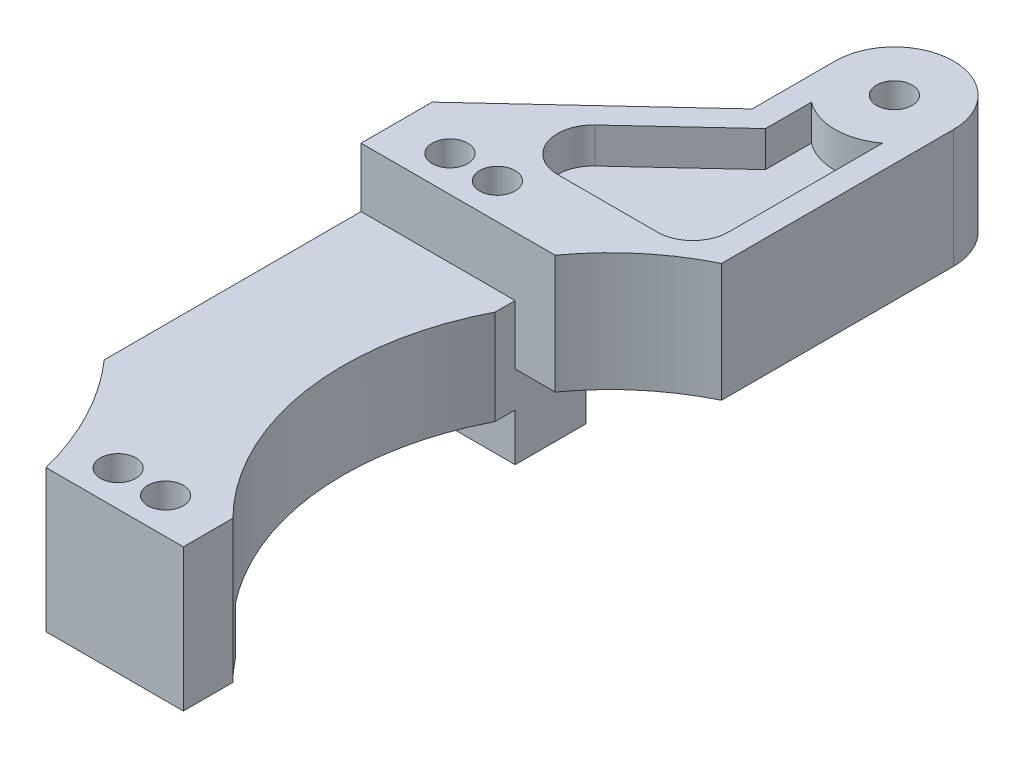
SolidWorks part; units mm, degrees
material "ABS"
ref_plane "Front Plane" through (0, 0, 0) normal (0, 0, 1) x (1, 0, 0)
ref_plane "Top Plane" through (0, 0, 0) normal (0, 1, 0) x (1, 0, 0)
ref_plane "Right Plane" through (0, 0, 0) normal (1, 0, 0) x (0, 0, -1)
sketch "Sketch1" plane through (0, -9, 0) normal (0, 1, 0) x (1, 0, 0)
  line L0 (27.1, 9) -> (31.1, 9) construction
  line L1 (23.1, 41) -> (27.1, 41) construction
  line L3 (22.6, 6) -> (35.6, 6)
  line L4 (22.6, 6) -> (22.6, 12)
  line L5 (22.6, 12) -> (35.6, 12)
  line L6 (35.6, 6) -> (35.6, 12)
  line L7 (22.6, 6) -> (35.6, 12) construction
  line L8 (22.6, 12) -> (35.6, 6) construction
  line L9 (18.6, 44) -> (31.6, 44)
  line L10 (18.6, 44) -> (18.6, 38)
  line L11 (18.6, 38) -> (31.6, 38)
  line L12 (31.6, 44) -> (31.6, 38)
  line L13 (18.6, 44) -> (31.6, 38) construction
  line L14 (18.6, 38) -> (31.6, 44) construction
  line L16 (-2.0823, -24.1604) -> (-2.1252, -24.6586)
  line L17 (-2.0823, -24.1604) -> (-2.1252, -24.6586)
  line L18 (18.6, 38) -> (31.6, 38)
  line L19 (18.6, 38) -> (18.6, 12)
  line L20 (18.6, 12) -> (31.6, 12)
  line L21 (31.6, 38) -> (31.6, 12)
  circle A2 centre (23.1, 41) radius 1.5
  circle A3 centre (23.1, 41) radius 1.5
  circle A5 centre (27.1, 41) radius 1.5
  circle A6 centre (27.1, 41) radius 1.5
  circle A8 centre (31.1, 9) radius 1.5
  circle A9 centre (31.1, 9) radius 1.5
  circle A10 centre (51.6, 26) radius 22.5
  circle A11 centre (27.1, 9) radius 1.5
  circle A12 centre (27.1, 9) radius 1.5
  arc A17 (-2.1252, -24.6586) -> (10.184, 22.5577) centre (0, 0) ccw
  arc A18 (-2.0823, -24.1604) -> (9.5544, 22.2885) centre (0, 0) ccw
  arc A19 (-2.1252, -24.6586) -> (10.184, 22.5577) centre (0, 0) ccw
  arc A20 (-2.0823, -24.1604) -> (9.5544, 22.2885) centre (0, 0) ccw
  spline S2 degree 3 poles (11.0692, -2972.4259) (11.0892, 37.2547) (10.6278, 22.7506) (10.1578, 22.5463) (10.1513, 22.5435) (10.1316, 22.535) (10.1185, 22.5293) (10.0793, 22.5123) (10.0531, 22.5009) (9.9745, 22.467) (9.9221, 22.4445) (-29.4113, 5.6252) (-87.2786, 32.2622) (-1166.4322, 2780.3784) knots -0.001495 -0.001495 -0.001495 -0.001495 0.000021 0.000021 0.000043 0.000043 0.000086 0.000086 0.000171 0.000171 0.000342 0.000342 0.128507 0.128507 0.128507 0.128507 only from (10.184, 22.5577) to (9.5544, 22.2885)
  spline S3 degree 3 poles (10.184, 22.5577) (10.1774, 22.5577) (10.1709, 22.552) (10.1578, 22.5463) (10.1513, 22.5435) (10.1316, 22.535) (10.1185, 22.5293) (10.0793, 22.5123) (10.0531, 22.5009) (9.9745, 22.467) (9.9221, 22.4445) (9.7647, 22.3772) (9.6596, 22.3327) (9.5544, 22.2885) knots 0 0 0 0 0.000021 0.000021 0.000043 0.000043 0.000086 0.000086 0.000171 0.000171 0.000342 0.000342 0.000685 0.000685 0.000685 0.000685
  point P2 (29.1, 9)
  point P20 (25.1, 41)
  point P25 (35.6, 9)
  dimension "D5" = 45
  dimension "D6" = 13
  dimension "D7" = 6
  dimension "D8" = 13
  dimension "D9" = 3
  dimension "D1" = 0
  dimension "D2" = 0
  dimension "D3" = 0
  dimension "D4" = 0
  dimension "D10" = 0
extrude "Boss-Extrude1" add sketch "Sketch1" along normal blind 4 contours L12 L9 L10 L11 A6 A3 | A19 L3 L6 A10 L5 L4 A12 A9 region at (29.2677, -9, -9.0229) region at (25.1, -9, -41)
extrude "Boss-Extrude2" add sketch "Sketch1<4>" along normal blind 8 from surface contours A19 L3 L6 A10 L5 L4 A12 A9 | A19 L20 L5 L21 A10 L11 L19 | A10 L21 L5 | A19 L4 L20 | L12 L9 L10 L11 A6 A3 region at (29.2677, -9, -9.0229) region at (22.2877, -9, -11.375) region at (24.5854, -9, -25.1582) region at (32.3675, -9, -13.1851) region at (25.1, -9, -41) starting at face at (27.1, -5, -39.5)
sketch "Sketch1<4>" plane through (0, -9, 0) normal (0, 1, 0) x (1, 0, 0) same geometry as "Sketch1"
sketch "Sketch2" plane through (0, 3, 0) normal (0, 1, 0) x (1, 0, 0)
  line L0 (12.6, 43) -> (12.6, 64) construction
  line L1 (17.6, 44) -> (31.6, 44)
  line L2 (17.6, 44) -> (17.6, 38)
  line L3 (17.6, 38) -> (31.6, 38)
  line L4 (31.6, 44) -> (31.6, 38)
  line L5 (7.6, 43) -> (7.6, 64)
  line L6 (17.6, 43) -> (17.6, 64)
  line L7 (21.6, 41) -> (28.6, 41) construction
  line L8 (12.6, 38) -> (17.6, 38)
  line L9 (17.6, 57) -> (30.1, 44)
  line L10 (25.1, 41) -> (25.1, 67.6639) construction
  line L11 (37.6, 43) -> (37.6, 64) construction
  line L12 (42.6, 43) -> (42.6, 64)
  line L13 (32.6, 43) -> (32.6, 64)
  line L14 (32.6, 57) -> (18.6, 44)
  line L15 (32.6, 38) -> (37.6, 38)
  line L16 (31.6, 38) -> (32.6, 38)
  line L17 (31.6, 38) -> (31.6, 44)
  line L18 (31.6, 44) -> (32.6, 44)
  line L19 (32.6, 38) -> (32.6, 44)
  circle A0 centre (12.6, 64) radius 1.5
  arc A1 (7.6, 43) -> (17.6, 43) centre (12.6, 43) ccw
  arc A2 (17.6, 64) -> (7.6, 64) centre (12.6, 64) ccw
  circle A3 centre (23.1, 41) radius 1.5 construction
  circle A4 centre (27.1, 41) radius 1.5 construction
  arc A5 (31.6, 36.3078) -> (35.6, 10.1807) centre (51.6, 26) ccw
  arc A6 (31.6, 36.3078) -> (35.6, 10.1807) centre (51.6, 26) ccw
  arc A7 (42.6, 43) -> (32.6, 43) centre (37.6, 43) cw
  arc A8 (32.6, 64) -> (42.6, 64) centre (37.6, 64) cw
  circle A9 centre (37.6, 64) radius 1.5
  point P10 (12.6, 53.5)
  point P31 (37.6, 53.5)
  circle M8 centre (27.1, 41) radius 1.5
  line M12 (31.6, 36.3078) -> (31.6, 44)
  line M13 (31.6, 44) -> (18.6, 44)
  line M14 (18.6, 44) -> (18.6, 16.328)
  circle M17 centre (23.1, 41) radius 1.5
  dimension "D1" = 3
  dimension "D2" = 10
  dimension "D3" = 21
  dimension "D4" = 5
  dimension "D5" = 5
  dimension "D6" = 13
  dimension "D7" = 6
  dimension "D8" = 1.5
  dimension "D10" = 24
  dimension "D11" = 13
  dimension "D9" = 0
extrude "Boss-Extrude3" add sketch "Sketch2" along normal blind 5 contours A8 L13 A7 L12 A9 | L18 L13 L14 L9 M13 | L9 L14 L1 | L3 L1 M14 M12 M13 M17 M8 | L15 A7 L19 | L16 L19 L13 L18 M12 region at (24.4585, 3, -45.8805) region at (25.1, 3, -41) region at (29.8581, 3, -49.692) region at (32.1, 3, -41) region at (37.6, 3, -53.2363) region at (33.7168, 3, -39.1168)
extrude "Boss-Extrude4" add sketch "Sketch2<3>" against normal blind 5 contours A8 L13 A7 L12 A9 | L18 L13 L14 L9 M13 | L9 L14 L1 | L16 L19 L13 L18 M12 | L15 A7 L19 region at (24.4585, 3, -45.8805) region at (29.8581, 3, -49.692) region at (32.1, 3, -41) region at (37.6, 3, -53.2363) region at (33.7168, 3, -39.1168)
sketch "Sketch2<3>" plane through (0, 3, 0) normal (0, 1, 0) x (1, 0, 0) same geometry as "Sketch2"
sketch "Sketch3" plane through (0, 8, 0) normal (0, 1, 0) x (1, 0, 0)
  line L10 (34.6, 56.1279) -> (20.6, 43.1279)
  line L11 (20.6, 43.1279) -> (20.6, 40)
  line L12 (20.6, 40) -> (37.6, 40)
  line L13 (40.6, 43) -> (40.6, 64)
  line L14 (34.6, 64) -> (34.6, 56.1279)
  line L15 (34.6, 56.1279) -> (20.6, 43.1279)
  line L16 (20.6, 43.1279) -> (20.6, 40)
  line L17 (20.6, 40) -> (37.6, 40)
  line L18 (40.6, 43) -> (40.6, 64)
  line L19 (34.6, 64) -> (34.6, 56.1279)
  line L20 (21.5392, 44) -> (40.6, 44)
  circle A2 centre (37.6, 64) radius 5
  arc A4 (37.6, 40) -> (40.6, 43) centre (37.6, 43) ccw
  arc A5 (40.6, 64) -> (34.6, 64) centre (37.6, 64) ccw
  arc A6 (37.6, 40) -> (40.6, 43) centre (37.6, 43) ccw
  arc A7 (40.6, 64) -> (34.6, 64) centre (37.6, 64) ccw
  dimension "D2" = 4
  dimension "D1" = 2
extrude "Cut-Extrude1" cut sketch "Sketch3" against normal blind 3 contours A2 L19 L15 L20 L18 region at (34.1964, 8, -49.9869)
fillet "Fillet3" radius 3 2 edges at (21.5392, 6.5, -44) (40.6, 6.5, -44)
sketch "Sketch4" plane through (0, 3, 0) normal (0, 1, 0) x (1, 0, 0)
  circle A1 centre (0, 0) radius 25.75
  arc A2 (24.0117, 6) -> (18.6, 16.328) centre (0, 0) ccw
  arc A3 (24.0117, 6) -> (18.6, 16.328) centre (0, 0) ccw
  circle A5 centre (51.6, 26) radius 20.5
  arc A6 (31.6, 36.3078) -> (35.6, 10.1807) centre (51.6, 26) ccw
  arc A7 (31.6, 36.3078) -> (35.6, 10.1807) centre (51.6, 26) ccw
  line M4 (18.6, 38) -> (18.6, 16.328)
  arc M5 (18.6, 16.328) -> (24.0117, 6) centre (0, 0) cw
  line M6 (24.0117, 6) -> (35.6, 6)
  dimension "D2" = 1
  dimension "D4" = 2
  dimension "D1" = 0
  dimension "D3" = 0
extrude "Cut-Extrude2" cut sketch "Sketch4" against normal through all both and the other way through all contours A1 M4 M6 M5 | A5 region at (-0.1351, 3, 0.0723) region at (51.6, 3, -26)
